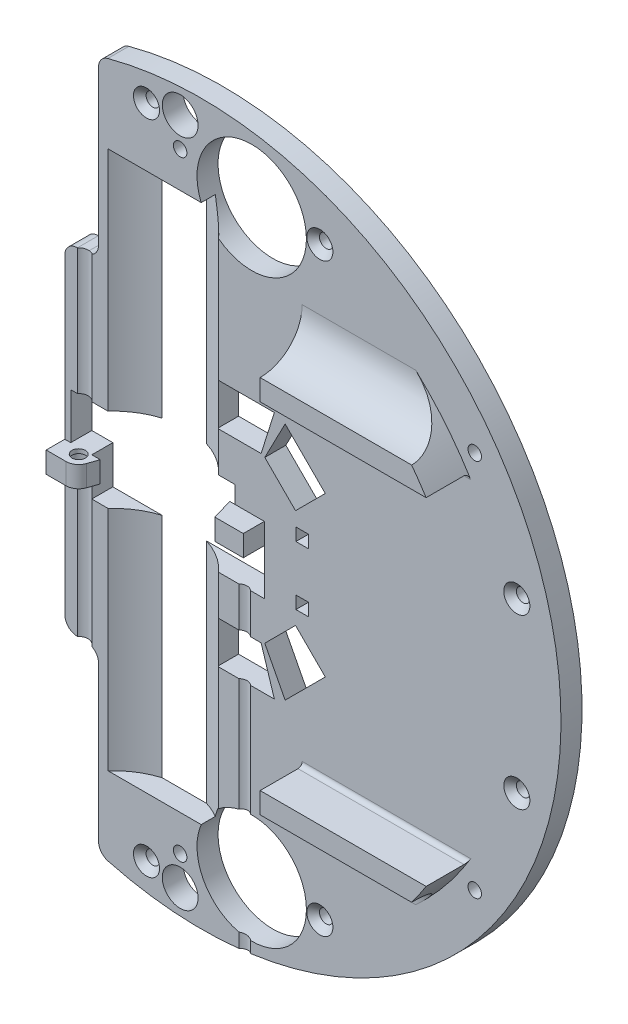
SolidWorks part; units mm, degrees
ref_plane "Front Plane" through (0, 0, 0) normal (1, 0, 0) x (0, 1, 0)
ref_plane "Top Plane" through (0, 0, 0) normal (0, 0, 1) x (0, 1, 0)
ref_plane "Right Plane" through (0, 0, 0) normal (0, 1, 0) x (-1, 0, 0)
sketch "Sketch1" plane through (0, 0, 0) normal (0, 0, 1) x (0, 1, 0)
  line L0 (0, 0) -> (0, -81.5088) construction
  line L1 (-40, 24.3888) -> (-40, 32.4114)
  line L2 (-40, 32.4114) -> (40, 32.4114)
  line L6 (-81.9478, 24.3888) -> (-40, 24.3888)
  line L7 (81.941, 24.4114) -> (40, 24.4114)
  line L8 (40, 24.4114) -> (40, 32.4114)
  arc A0 (-81.9478, 24.3888) -> (81.941, 24.4114) centre (0, 0) ccw
  circle A1 centre (-20, -75) radius 1.6
  circle A2 centre (20, -75) radius 1.6
  circle A3 centre (-69.5, -28.2) radius 1.6
  circle A9 centre (-78, 13) radius 1.6
  circle A10 centre (-79.5, 5) radius 4.25
  circle A11 centre (-69, -12) radius 13
  circle A16 centre (69, -12) radius 13
  circle A17 centre (79.5, 5) radius 4.25
  circle A18 centre (78, 13) radius 1.6
  circle A19 centre (69.5, -28.2) radius 1.6
  dimension "D1" = 171
  dimension "D3" = 3.2
  dimension "D7" = 3.2
  dimension "D8" = 78
  dimension "D13" = 5
  dimension "D14" = 69
  dimension "D16" = 40
  dimension "D2" = 75
  dimension "D4" = 20
  dimension "D5" = 69.5
  dimension "D6" = 28.2
  dimension "D9" = 40
  dimension "D10" = 13
  dimension "D11" = 8
  dimension "D12" = 79.5
  dimension "D15" = 12
extrude "Boss-Extrude2" add sketch "Sketch1" along normal blind 5
sketch "Sketch2" plane through (0, 0, 5) normal (0, 0, 1) x (1, 0, 0)
  line L1 (60, 45) -> (24, 45)
  line L3 (63.4429, 40) -> (24, 40)
  line L4 (24, 45) -> (24, 40)
  line L6 (24, -45) -> (24, -40)
  line L7 (63.4429, -40) -> (24, -40)
  line L8 (60, -45) -> (24, -45)
  arc A3 (60, -45) -> (63.4429, -40) centre (0, 0) ccw
  arc A4 (63.4429, 40) -> (60, 45) centre (0, 0) ccw
  dimension "D1" = 150
  dimension "D2" = 40
extrude "Boss-Extrude3" add sketch "Sketch2" along normal blind 10
fillet "Fillet1" radius 10 2 edges at (42, -45, 5) (42, 45, 5)
fillet "Fillet2" radius 1 2 edges at (43.7214, -40, 5) (43.7214, 40, 5)
sketch "Sketch5" plane through (0, 0, 5) normal (0, 0, 1) x (1, 0, 0)
  line L0 (0, 0) -> (93.3614, 0) construction
  circle A0 centre (65, 45) radius 1.6
  circle A2 centre (-5, 72.5) radius 1.6
  circle A4 centre (65, -45) radius 1.6
  circle A5 centre (-5, -72.5) radius 1.6
  dimension "D1" = 3.2
  dimension "D5" = 3.2
  dimension "D2" = 65
  dimension "D3" = 45
  dimension "D4" = 5
  dimension "D6" = 72.5
extrude "Cut-Extrude2" cut sketch "Sketch5" against normal blind 10
chamfer "Chamfer1" distance 1.5 angle 45 6 edges at (-14.6, -78, 5) (29.8, -69.5, 5) (76.6, -20, 5) (73.4, 20, 5) (26.6, 69.5, 5) (-11.4, 78, 5)
chamfer "Chamfer2" distance 1.5 angle 45 4 edges at (-3.4, 72.5, 0) (-3.4, -72.5, 0) (66.6, -45, 0) (66.6, 45, 0)
sketch "Sketch9" plane through (0, 0, 5) normal (0, 0, 1) x (1, 0, 0)
  line L1 (17.112, -24.1831) -> (24.1831, -17.112) construction
  line L6 (14.2376, -19.4864) -> (3.8798, -19.4864)
  line L8 (15.1085, -19.1155) -> (22.4153, -11.8087)
  line L10 (22.4153, -11.8087) -> (29.4864, -18.8798)
  line L11 (19.9404, -28.4257) -> (29.4864, -18.8798)
  line L12 (11.8087, -22.4153) -> (29.4864, -18.8798) construction
  line L13 (22.4153, -11.8087) -> (18.8798, -29.4864) construction
  line L14 (0, 0) -> (90.6538, 0) construction
  line L23 (17.3798, -29.4864) -> (3.8798, -29.4864)
  line L24 (3.8798, -19.4864) -> (3.8798, -29.4864)
  line L25 (18.8798, -19.4864) -> (3.8798, -29.4864) construction
  line L26 (18.8798, -29.4864) -> (3.8798, -19.4864) construction
  line L32 (15.1085, -19.1155) -> (19.9404, -28.4257)
  line L33 (17.3798, -29.4864) -> (14.2376, -19.4864)
  line L34 (17.3798, 29.4864) -> (14.2376, 19.4864)
  line L35 (14.2376, 19.4864) -> (3.8798, 19.4864)
  line L36 (3.8798, 19.4864) -> (3.8798, 29.4864)
  line L37 (17.3798, 29.4864) -> (3.8798, 29.4864)
  line L38 (15.1085, 19.1155) -> (19.9404, 28.4257)
  line L39 (15.1085, 19.1155) -> (22.4153, 11.8087)
  line L40 (22.4153, 11.8087) -> (29.4864, 18.8798)
  line L41 (19.9404, 28.4257) -> (29.4864, 18.8798)
  point P1 (11.3798, -24.4864)
  point P6 (20.6475, -20.6475)
  dimension "D1" = 10
  dimension "D2" = 15
  dimension "D3" = 15
  dimension "D4" = 10
  dimension "D6" = 1.5
  dimension "D7" = 1.5
extrude "Cut-Extrude3" cut sketch "Sketch9" against normal blind 10
sketch "Sketch10" plane through (0, 0, 0) normal (0, 1, 0) x (-1, 0, 0)
  line L0 (-85.5, 0) -> (24.4114, 0) construction
  circle A0 centre (9, 17) radius 17.8
  dimension "D1" = 35.6
  dimension "D2" = 17
  dimension "D3" = 9
extrude "Cut-Extrude4" cut sketch "Sketch10" against normal blind 64 and the other way blind 64
sketch "Sketch11" plane through (0, 0, 5) normal (0, 0, 1) x (1, 0, 0)
  line L0 (-26, -0.9) -> (-31, -0.9)
  line L1 (8, 10) -> (-25, 10)
  line L3 (15, -10) -> (-26, -10)
  line L4 (-26, -0.9) -> (-26, -10)
  line L5 (15, -10) -> (15, 0.9)
  line L6 (8, 10) -> (8, 0.9)
  line L7 (8, 0.9) -> (15, 0.9)
  line L8 (-31, -0.9) -> (-31, 10)
  line L9 (-31, 10) -> (-25, 10)
  point P0 (0, 0)
  dimension "D1" = 20
  dimension "D2" = 10
  dimension "D3" = 6
  dimension "D4" = 15
  dimension "D5" = 7
  dimension "D6" = 0.9
  dimension "D7" = 0.9
  dimension "D8" = 5
extrude "Cut-Extrude5" cut sketch "Sketch11" against normal blind 62.5
sketch "Sketch12" plane through (0, 0, 5) normal (0, 0, 1) x (1, 0, 0)
  line L1 (10.2402, 0) -> (10.2402, 0.9) construction
  line L2 (-6.5732, 0) -> (-6.5732, 0.9) construction
  line L3 (-6.5732, 0.9) -> (10.2402, 0.9) construction
  line L4 (-16.3028, 0) -> (-16.3028, -0.9) construction
  line L5 (-8.6264, 0) -> (-8.6264, -0.9) construction
  dimension "D1" = 0.9
  dimension "D2" = 0.9
ref_plane "Plane2" through (0, 0.9, 0) normal (0, -1, 0) x (1, 0, 0)
sketch "Sketch13" plane through (0, 0, 5) normal (0, 0, 1) x (1, 0, 0)
  line L0 (-6.5732, 0.9) -> (10.2402, 0.9) construction
  line L1 (15, 0.9) -> (6.7929, 0.9)
  line L2 (15, 0.9) -> (15, 5.9)
  line L3 (15, 5.9) -> (6.7929, 5.9)
  line L4 (6.7929, 0.9) -> (6.7929, 5.9)
  dimension "D1" = 5
extrude "Boss-Extrude4" add sketch "Sketch13" along normal blind 5
sketch "Sketch14" plane through (0, 0.9, 0) normal (0, -1, 0) x (1, 0, 0)
  circle A1 centre (10.3299, 6.4392) radius 2
  dimension "D2" = 4
extrude "Cut-Extrude6" cut sketch "Sketch14" against normal blind 4 and the other way blind 110
sketch "Sketch15" plane through (0, 0.9, 0) normal (0, -1, 0) x (1, 0, 0)
  line L2 (6.7929, 5) -> (6.7929, 10)
  line L3 (6.7929, 10) -> (8.2341, 10)
  line L4 (6.7929, 5) -> (8.2341, 10)
extrude "Cut-Extrude7" cut sketch "Sketch15" against normal blind 15
sketch "Sketch16" plane through (0, 0, 5) normal (0, 0, 1) x (1, 0, 0)
  line L0 (-32.4114, 40) -> (-32.4114, -40) construction
  line L1 (-32.4114, -0.9) -> (-24, -0.9)
  line L2 (-32.4114, -0.9) -> (-32.4114, -5.9)
  line L3 (-32.4114, -5.9) -> (-24, -5.9)
  line L4 (-24, -0.9) -> (-24, -5.9)
  dimension "D1" = 5
extrude "Boss-Extrude5" add sketch "Sketch16" along normal blind 5
sketch "Sketch17" plane through (0, -5.9, 0) normal (0, -1, 0) x (1, 0, 0)
  circle A0 centre (-27.6683, 6.4392) radius 2.25
  dimension "D1" = 4.5
extrude "Cut-Extrude8" cut sketch "Sketch17" against normal blind 4 and the other way blind 40
sketch "Sketch18" plane through (0, -5.9, 0) normal (0, -1, 0) x (1, 0, 0)
  line L0 (-24, 5) -> (-24.8314, 7.4156)
  line L1 (-32.4114, 10) -> (-24, 10) construction
  line L2 (-25.7209, 10) -> (-24, 10)
  line L3 (-24, 10) -> (-24, 5)
  line L5 (-27.6683, 9.4394) -> (-32.4114, 9.4394)
  line L6 (-32.4114, 10) -> (-32.4114, 5) construction
  line L7 (-32.4114, 9.4394) -> (-32.4114, 10)
  line L8 (-32.4114, 10) -> (-25.7209, 10)
  arc A1 (-24.8314, 7.4156) -> (-27.6683, 9.4394) centre (-27.6683, 6.4392) ccw
extrude "Cut-Extrude9" cut sketch "Sketch18" against normal blind 7
sketch "Sketch19" plane through (0, -1.9, 0) normal (0, -1, 0) x (1, 0, 0)
  circle A0 centre (-27.6683, 6.4392) radius 1.6
  dimension "D1" = 3.2
extrude "Cut-Extrude10" cut sketch "Sketch19" against normal blind 7
sketch "Sketch20" plane through (0, -0.9, 0) normal (0, 1, 0) x (-1, 0, 0)
  circle A0 centre (27.6683, 6.4392) radius 2.25
  dimension "D1" = 4.5
extrude "Cut-Extrude11" cut sketch "Sketch20" along normal blind 45
sketch "Sketch21" plane through (0, 0, 0) normal (0, 0, -1) x (1, 0, 0)
  line L1 (69.738, 4) -> (6.369, 4)
  line L2 (69.738, 4) -> (69.738, -4)
  line L3 (69.738, -4) -> (6.369, -4)
  line L4 (6.369, 4) -> (6.369, -4)
  dimension "D1" = 8
  dimension "D2" = 4
extrude "Cut-Extrude12" cut sketch "Sketch21" against normal blind 3
sketch "Sketch22" plane through (0, 0, 0) normal (0, 0, -1) x (1, 0, 0)
  line L0 (0, 0) -> (46.1564, 0) construction
  line L1 (22.5, -5.5) -> (25.5, -5.5)
  line L2 (22.5, -5.5) -> (22.5, -8.5)
  line L3 (22.5, -8.5) -> (25.5, -8.5)
  line L4 (25.5, -5.5) -> (25.5, -8.5)
  line L5 (22.5, -5.5) -> (25.5, -8.5) construction
  line L6 (22.5, -8.5) -> (25.5, -5.5) construction
  line L11 (22.5, 8.5) -> (25.5, 5.5) construction
  line L12 (22.5, 5.5) -> (25.5, 8.5) construction
  line L13 (25.5, 5.5) -> (25.5, 8.5)
  line L14 (22.5, 8.5) -> (25.5, 8.5)
  line L15 (22.5, 5.5) -> (22.5, 8.5)
  line L16 (22.5, 5.5) -> (25.5, 5.5)
  point P0 (24, -7)
  point P12 (24, 7)
  dimension "D1" = 3
  dimension "D2" = 3
  dimension "D3" = 7
  dimension "D4" = 24
extrude "Cut-Extrude13" cut sketch "Sketch22" against normal blind 5
sketch "Sketch23" plane through (0, 0, 5) normal (0, 0, 1) x (1, 0, 0)
fillet "Fillet3" radius 3 6 edges at (-24.3888, -40, 2.5) (-32.4114, -40, 2.5) (-24.4114, 40, 2.5) (-32.4114, 40, 2.5) (-24.4114, 81.941, 2.5) (-24.3888, -81.9478, 2.5)
